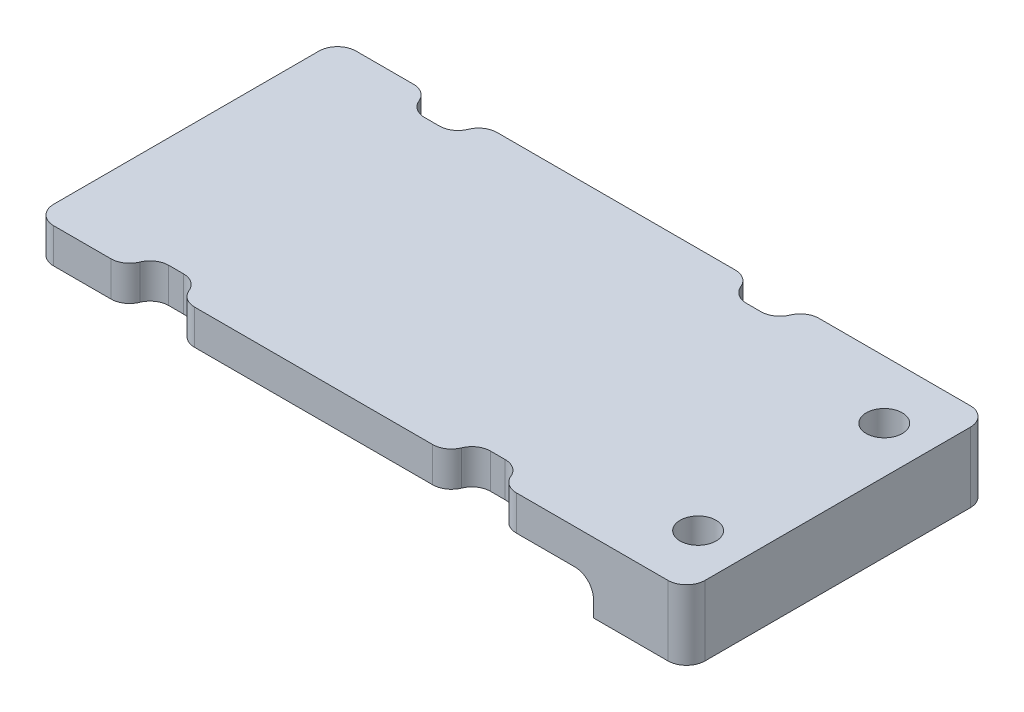
SolidWorks part; units mm, degrees
ref_plane "Front" through (0, 0, 0) normal (0, 0, 1) x (1, 0, 0)
ref_plane "Top" through (0, 0, 0) normal (0, 1, 0) x (1, 0, 0)
ref_plane "Right" through (0, 0, 0) normal (1, 0, 0) x (0, 0, -1)
sketch "Sketch1" plane through (0, 0, 0) normal (0, 1, 0) x (1, 0, 0)
  line L1 (-44.45, -20.6375) -> (44.45, -20.6375)
  line L2 (-44.45, -20.6375) -> (-44.45, 20.6375)
  line L3 (-44.45, 20.6375) -> (44.45, 20.6375)
  line L4 (44.45, -20.6375) -> (44.45, 20.6375)
  line L5 (-44.45, -20.6375) -> (44.45, 20.6375) construction
  line L6 (-44.45, 20.6375) -> (44.45, -20.6375) construction
  point P0 (0, 0)
  dimension "D1" = 88.9
  dimension "D2" = 41.275
extrude "Boss-Extrude1" add sketch "Sketch1" along normal blind 4.7625
sketch "Sketch3" plane through (0, 0, 0) normal (0, -1, 0) x (1, 0, 0)
  line L0 (44.45, -20.6375) -> (-44.45, -20.6375) construction
  line L1 (44.45, 20.6375) -> (31.75, 20.6375)
  line L2 (44.45, 20.6375) -> (44.45, -20.6375)
  line L3 (44.45, -20.6375) -> (31.75, -20.6375)
  line L4 (31.75, 20.6375) -> (31.75, -20.6375)
  dimension "D1" = 12.7
extrude "Boss-Extrude2" add sketch "Sketch3" along normal blind 4.7625
sketch "Sketch8" plane through (0, 4.7625, 0) normal (0, 1, 0) x (1, 0, 0)
  line L4 (44.45, -20.6375) -> (44.45, 20.6375) construction
  line L5 (-50, 0) -> (50, 0) construction
  point P0 (38.1, 12.7)
  point P4 (38.1, -12.7)
  dimension "D1" = 25.4
  dimension "D2" = 12.7
  dimension "D3" = 6.35
hole_wizard "#10 (0.1935) Diameter Hole1" positions "Sketch8" profile "Sketch7" hole size "#10" standard "ANSI Inch" end condition through all
sketch "Sketch7" plane through (38.1, 4.7625, -12.7) normal (1, 0, 0) x (0, 0, 1)
  line L0 (0, 0) -> (0, 9.525)
  line L1 (0, 9.525) -> (2.4574, 9.525)
  line L2 (2.4574, 9.525) -> (2.4574, 0)
  line L5 (2.4574, 0) -> (0, 0)
  line L11 (0, -6.35) -> (0, 107.95) construction
  dimension "Thru Hole Dia." = 4.9149
  dimension "Thru Hole Depth" = 9.525
sketch "Sketch9" plane through (0, 4.7625, 0) normal (0, 1, 0) x (1, 0, 0)
  line L14 (44.45, 20.6375) -> (-44.45, 20.6375) construction
  line L20 (12.3597, 20.6375) -> (18.7097, 20.6375)
  line L21 (12.3597, 20.6375) -> (12.3597, 17.4625)
  line L22 (12.3597, 17.4625) -> (18.7097, 17.4625)
  line L23 (18.7097, 20.6375) -> (18.7097, 17.4625)
  line L24 (-44.45, -20.6375) -> (44.45, -20.6375) construction
  line L25 (-31.5516, 20.6375) -> (-25.2016, 20.6375)
  line L26 (-31.5516, 20.6375) -> (-31.5516, 17.4625)
  line L27 (-31.5516, 17.4625) -> (-25.2016, 17.4625)
  line L28 (-25.2016, 20.6375) -> (-25.2016, 17.4625)
  line L29 (-31.5516, -20.6375) -> (-25.2016, -20.6375)
  line L30 (-31.5516, -20.6375) -> (-31.5516, -17.4625)
  line L31 (-31.5516, -17.4625) -> (-25.2016, -17.4625)
  line L32 (-25.2016, -20.6375) -> (-25.2016, -17.4625)
  line L34 (12.3597, -20.6375) -> (18.7097, -20.6375)
  line L35 (12.3597, -20.6375) -> (12.3597, -17.4625)
  line L36 (12.3597, -17.4625) -> (18.7097, -17.4625)
  line L37 (18.7097, -20.6375) -> (18.7097, -17.4625)
  line L38 (44.45, -20.6375) -> (44.45, 20.6375) construction
  dimension "D1" = 3.175
  dimension "D2" = 6.35
  dimension "D3" = 37.5613
  dimension "D4" = 76.0016
extrude "Cut-Extrude1" cut sketch "Sketch9" against normal through all
fillet "Fillet1" radius 2.54 13 edges at (31.75, 0, 0) (-25.2016, 2.3812, 20.6375) (-31.5516, 2.3812, 20.6375) (-44.45, 2.3813, 20.6375) (-31.5516, 2.3812, -20.6375) (-25.2016, 2.3812, -20.6375) (12.3597, 2.3812, -20.6375) (18.7097, 2.3812, -20.6375) (44.45, 0, -20.6375) (44.45, 0, 20.6375) (18.7097, 2.3812, 20.6375) (12.3597, 2.3812, 20.6375) (-44.45, 2.3813, -20.6375)
fillet "Fillet2" radius 2.54 8 edges at (18.7097, 2.3813, -17.4625) (12.3597, 2.3812, -17.4625) (-31.5516, 2.3812, -17.4625) (-25.2016, 2.3813, -17.4625) (-25.2016, 2.3813, 17.4625) (-31.5516, 2.3812, 17.4625) (12.3597, 2.3812, 17.4625) (18.7097, 2.3813, 17.4625)
